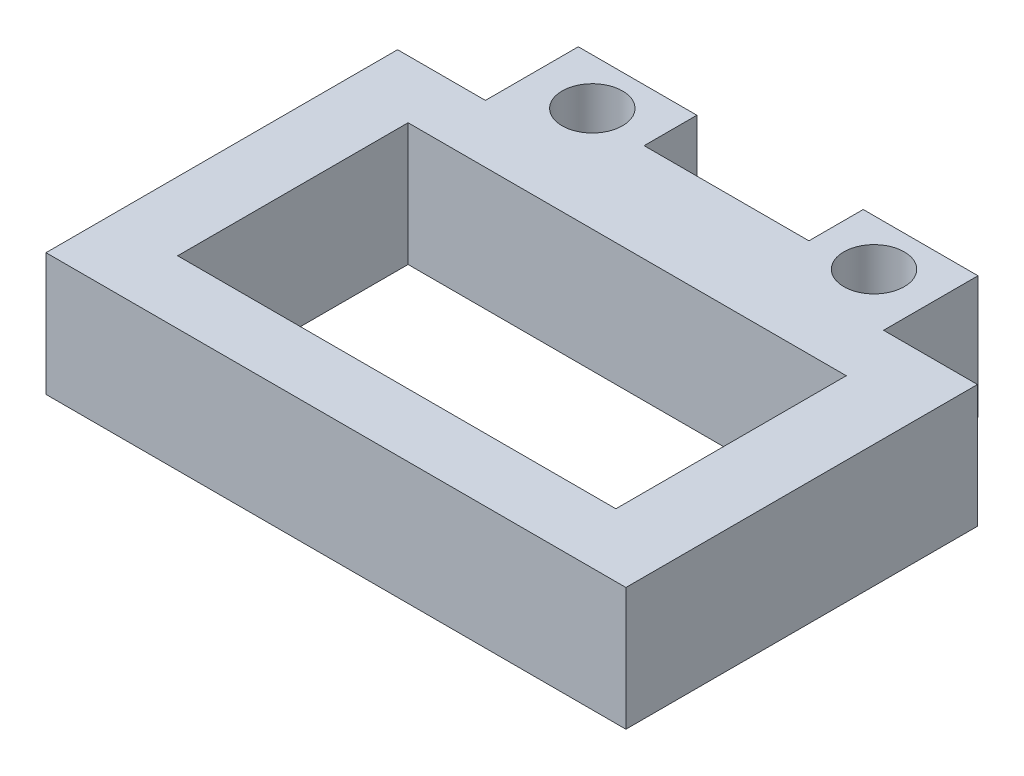
SolidWorks part; units mm, degrees
ref_plane "Front Plane" through (0, 0, 0) normal (0, 0, 1) x (1, 0, 0)
ref_plane "Top Plane" through (0, 0, 0) normal (0, 1, 0) x (1, 0, 0)
ref_plane "Right Plane" through (0, 0, 0) normal (1, 0, 0) x (0, 0, -1)
sketch "Sketch1" plane through (0, 0, 0) normal (0, 1, 0) x (1, 0, 0)
  line L0 (23.2084, 35.6929) -> (23.2084, 32.9001)
  line L1 (15.9084, 27.7029) -> (39.1084, 27.7029)
  line L2 (15.9084, 27.7029) -> (15.9084, 15.5029)
  line L3 (15.9084, 15.5029) -> (39.1084, 15.5029)
  line L4 (39.1084, 27.7029) -> (39.1084, 15.5029)
  line L5 (12.281, 30.7738) -> (42.9837, 30.7738)
  line L6 (12.281, 30.7738) -> (12.281, 12.1599)
  line L7 (12.281, 12.1599) -> (42.9837, 12.1599)
  line L8 (42.9837, 30.7738) -> (42.9837, 12.1599)
  line L9 (31.8568, 35.6929) -> (31.8949, 35.6929)
  line L10 (16.9304, 35.6929) -> (16.9304, 30.7738)
  line L11 (16.9304, 30.7738) -> (38.0106, 30.7738)
  line L12 (38.0106, 35.7738) -> (38.0106, 30.7738)
  line L13 (23.2084, 32.9001) -> (31.933, 32.9001)
  line L14 (31.933, 32.9001) -> (31.933, 35.7738)
  line L15 (16.9304, 35.6929) -> (23.2084, 35.6929)
  line L16 (31.933, 35.7738) -> (38.0106, 35.7738)
  circle A0 centre (20.1262, 33.2384) radius 1.6
  circle A1 centre (34.9615, 33.3193) radius 1.6
  point P17 (0, 0)
  point P18 (38.0106, 35.7738)
  point P19 (16.9304, 35.6929)
  dimension "D4" = 3.2
  dimension "D5" = 3.2
  dimension "D1" = 23.2
  dimension "D2" = 12.2
  dimension "D3" = 5
extrude "Boss-Extrude5" add sketch "Sketch1" along normal blind 6.5 contours L8 L5 L6 L7 L1 L4 L3 L2 | L16 L14 L13 L0 L15 L10 L5 L12 region at (27.4716, 0, -32.8348) region at (27.4705, 0, -30.4148)
